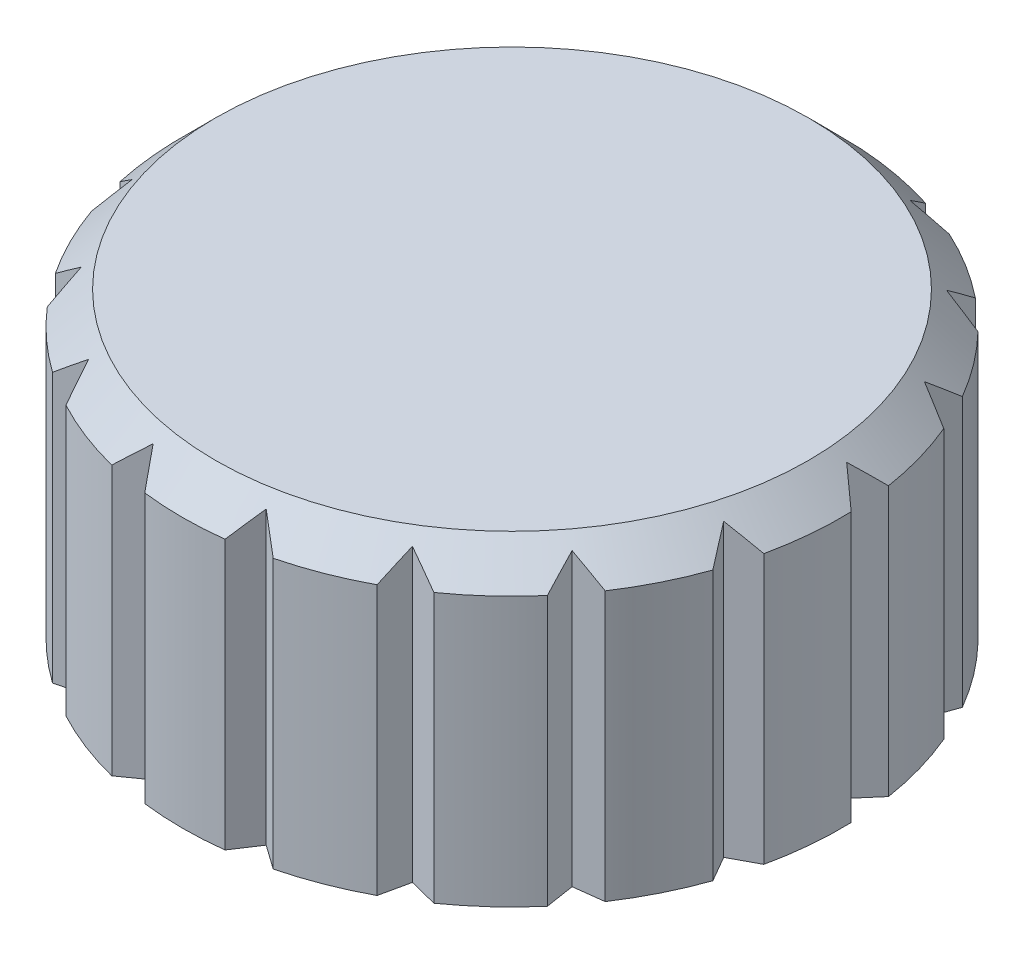
SolidWorks part; units mm, degrees
ref_plane "Front Plane" through (0, 0, 0) normal (0, 0, 1) x (1, 0, 0)
ref_plane "Top Plane" through (0, 0, 0) normal (0, 1, 0) x (1, 0, 0)
ref_plane "Right Plane" through (0, 0, 0) normal (1, 0, 0) x (0, 0, -1)
sketch "Sketch1" plane through (0, 0, 0) normal (0, 1, 0) x (1, 0, 0)
  line L0 (0, 0) -> (0, 12) construction
  line L1 (-3, 14.2987) -> (0, 11.2)
  line L2 (0, 11.2) -> (3, 14.2987)
  line L3 (3, 14.2987) -> (-3, 14.2987)
  circle A0 centre (0, 0) radius 10
  circle A1 centre (0, 0) radius 12
  dimension "D1" = 20
  dimension "D2" = 2
  dimension "D3" = 0.8
  dimension "D4" = 6
extrude "Boss-Extrude1" add sketch "Sketch1" along normal blind 8 contours A0 L1 A1 L2 | L0 L2 A1 | L1 L0 A1 region at (-0.2518, 0, -11.7281) region at (0.6196, 0, -11.3522) region at (0.2518, 0, -11.7281)
extrude "Boss-Extrude2" add sketch "Sketch1<2>" along normal blind 3 from surface contours A0 | A1 A0 | L0 L2 A1 | L1 L0 A1 region at (-0.2518, 0, -11.7281) region at (6.8711, 0, -6.8711) region at (0.6196, 0, -11.3522) region at (0.2518, 0, -11.7281) starting at face at (0, 8, 12)
sketch "Sketch1<2>" plane through (0, 0, 0) normal (0, 1, 0) x (1, 0, 0) same geometry as "Sketch1"
chamfer "Chamfer1" distance 1.2 angle 45 1 edges at (0, 11, 12)
extrude "Cut-Extrude1" cut sketch "Sketch1<4>" along normal through all contours L1 L0 A1 | L0 L2 A1 region at (-0.2518, 0, -11.7281) region at (0.2518, 0, -11.7281)
sketch "Sketch1<4>" plane through (0, 0, 0) normal (0, 1, 0) x (1, 0, 0) same geometry as "Sketch1"
pattern_circular "CirPattern1" count 17 over 360 about axis through (0, 11, 0) along (0, 1, 0) of "Cut-Extrude1"
thread "Thread1" pitch 2 method extrude trim with start face yes trim with end face yes profile "Thread Profile1" start angle 0, offset 2, length 10, pitch 2, diameter 20
ref_plane "Plane1" through (10, -2, 0) normal (0, 0, 1) x (1, 0, 0)
sketch "Thread Profile1" plane through (10, -2, 0) normal (0, 0, 1) x (1, 0, 0)
  line L0 (0, 0) -> (0, 2) construction
  line L11 (0, 0) -> (0, 1.75)
  line L12 (0, 1.75) -> (-1.0825, 1.125)
  line L13 (-1.0825, 1.125) -> (-1.0825, 0.625)
  line L15 (-1.0825, 0.625) -> (0, 0)
  line L17 (-1.0825, 0.875) -> (0, 0.875) construction
  point P2 (0, 0)
  dimension "Pitch" = 2
  dimension "Profile_Angle" = 60
  dimension "Profile_Land" = 0.5
  dimension "Profile_Height" = 1.0825
sketch "Sketch2" plane through (0, 8, 0) normal (0, -1, 0) x (1, 0, 0)
  circle A0 centre (0, 0) radius 7.5
  dimension "D1" = 15
extrude "Boss-Extrude3" add sketch "Sketch2" along normal blind 2
chamfer "Chamfer2" distance 2 angle 45 1 edges at (0, 6, -7.5)
